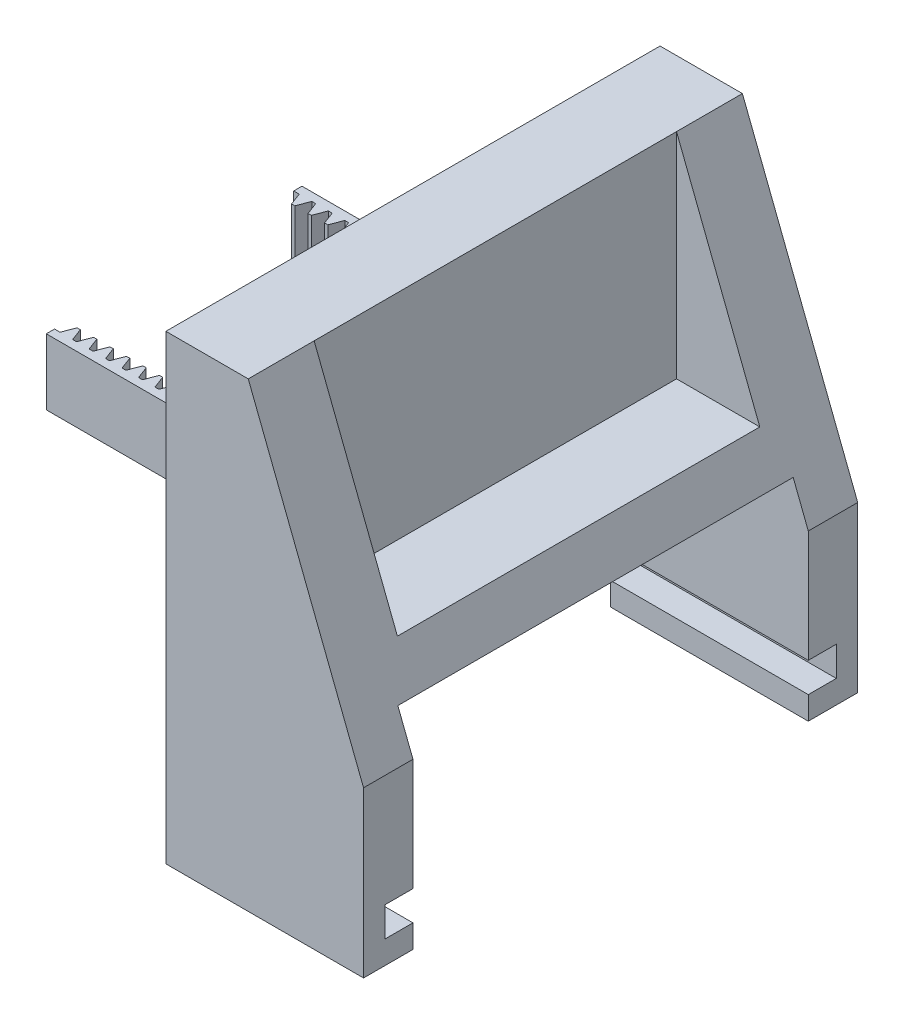
SolidWorks part; units mm, degrees
ref_plane "Front Plane" through (0, 0, 0) normal (0, 0, 1) x (1, 0, 0)
ref_plane "Top Plane" through (0, 0, 0) normal (0, 1, 0) x (1, 0, 0)
ref_plane "Right Plane" through (0, 0, 0) normal (1, 0, 0) x (0, 0, -1)
sketch "Sketch1" plane through (0, 0, 0) normal (0, 0, 1) x (1, 0, 0)
  line L0 (0, 0) -> (0, -28)
  line L1 (0, -28) -> (12, -28)
  line L2 (12, -28) -> (12, -18)
  line L3 (12, -18) -> (5, 0)
  line L4 (5, 0) -> (0, 0)
  dimension "D1" = 28
  dimension "D2" = 12
  dimension "D3" = 10
  dimension "D4" = 5
extrude "Boss-Extrude1" add sketch "Sketch1" against normal blind 30
sketch "Sketch4" plane through (0, 0, 0) normal (-1, 0, 0) x (0, 0, 1)
  line L0 (-30, 0) -> (-30, -28) construction
  line L1 (-27, -15.6386) -> (-3, -15.6386)
  line L2 (-27, -15.6386) -> (-27, -29.6386)
  line L3 (-27, -29.6386) -> (-3, -29.6386)
  line L4 (-3, -15.6386) -> (-3, -29.6386)
  point P4 (-27, -22.6386)
  dimension "D1" = 24
  dimension "D2" = 14
  dimension "D3" = 3
extrude "Cut-Extrude2" cut sketch "Sketch4" against normal blind 25 contours L2 L1 L4 L3
sketch "Sketch5" plane through (0, 0, 0) normal (-1, 0, 0) x (0, 0, 1)
  line L0 (-3, -15.6386) -> (-3, -28) construction
  line L1 (-3, -24.8) -> (-1.3, -24.8)
  line L2 (-3, -24.8) -> (-3, -26.6)
  line L3 (-3, -26.6) -> (-1.3, -26.6)
  line L4 (-1.3, -24.8) -> (-1.3, -26.6)
  line L5 (-3, -28) -> (0, -28) construction
  dimension "D1" = 1.8
  dimension "D2" = 1.7
  dimension "D3" = 1.4
extrude "Cut-Extrude3" cut sketch "Sketch5" against normal blind 15
ref_plane "Plane1" through (0, 0, -15) normal (0, 0, 1) x (1, 0, 0)
mirror "Mirror1" about plane through (0, 0, -15) normal (0, 0, 1) of "Cut-Extrude3"
sketch "Sketch6" plane through (0, 0, -15) normal (0, 0, 1) x (1, 0, 0)
  line L0 (5, 0) -> (5, -13)
  line L1 (5, -13) -> (10.0556, -13)
  line L2 (12, -18) -> (5, 0) construction
  line L3 (10.0556, -13) -> (5, 0)
  dimension "D1" = 13
extrude "Cut-Extrude4" cut sketch "Sketch6" against normal mid plane 22
ref_plane "Plane2" through (0, -15, 0) normal (0, 1, 0) x (1, 0, 0)
sketch "Sketch7" plane through (0, -15, 0) normal (0, 1, 0) x (1, 0, 0)
  line L0 (0, 22.7609) -> (-14.5, 22.7609)
  line L1 (0, 30) -> (0, 0) construction
  line L2 (-14.5, 22.7609) -> (-14.5, 22.2609)
  line L3 (0, 22.7609) -> (0, 22.2609)
  line L4 (0, 22.2609) -> (-0.4, 22.2609)
  line L5 (-0.8812, 21.5119) -> (-1.1644, 22.2609)
  line L6 (-0.4, 22.2609) -> (-0.6812, 21.5119)
  line L7 (-0.6812, 21.5119) -> (-0.8812, 21.5119)
  line L8 (-1.8812, 21.5119) -> (-2.1644, 22.2609)
  line L9 (-1.6812, 21.5119) -> (-1.8812, 21.5119)
  line L10 (-1.4, 22.2609) -> (-1.6812, 21.5119)
  line L11 (-2.8812, 21.5119) -> (-3.1644, 22.2609)
  line L12 (-2.6812, 21.5119) -> (-2.8812, 21.5119)
  line L13 (-2.4, 22.2609) -> (-2.6812, 21.5119)
  line L14 (-3.8812, 21.5119) -> (-4.1644, 22.2609)
  line L15 (-3.6812, 21.5119) -> (-3.8812, 21.5119)
  line L16 (-3.4, 22.2609) -> (-3.6812, 21.5119)
  line L17 (-4.8812, 21.5119) -> (-5.1644, 22.2609)
  line L18 (-4.6812, 21.5119) -> (-4.8812, 21.5119)
  line L19 (-4.4, 22.2609) -> (-4.6812, 21.5119)
  line L20 (-5.8812, 21.5119) -> (-6.1644, 22.2609)
  line L21 (-5.6812, 21.5119) -> (-5.8812, 21.5119)
  line L22 (-5.4, 22.2609) -> (-5.6812, 21.5119)
  line L23 (-6.8812, 21.5119) -> (-7.1644, 22.2609)
  line L24 (-6.6812, 21.5119) -> (-6.8812, 21.5119)
  line L25 (-6.4, 22.2609) -> (-6.6812, 21.5119)
  line L26 (-7.8812, 21.5119) -> (-8.1644, 22.2609)
  line L27 (-7.6812, 21.5119) -> (-7.8812, 21.5119)
  line L28 (-7.4, 22.2609) -> (-7.6812, 21.5119)
  line L29 (-8.8812, 21.5119) -> (-9.1644, 22.2609)
  line L30 (-8.6812, 21.5119) -> (-8.8812, 21.5119)
  line L31 (-8.4, 22.2609) -> (-8.6812, 21.5119)
  line L32 (-9.8812, 21.5119) -> (-10.1644, 22.2609)
  line L33 (-9.6812, 21.5119) -> (-9.8812, 21.5119)
  line L34 (-9.4, 22.2609) -> (-9.6812, 21.5119)
  line L35 (-10.8812, 21.5119) -> (-11.1644, 22.2609)
  line L36 (-10.6812, 21.5119) -> (-10.8812, 21.5119)
  line L37 (-10.4, 22.2609) -> (-10.6812, 21.5119)
  line L38 (-11.8812, 21.5119) -> (-12.1644, 22.2609)
  line L39 (-11.6812, 21.5119) -> (-11.8812, 21.5119)
  line L40 (-11.4, 22.2609) -> (-11.6812, 21.5119)
  line L41 (-12.8812, 21.5119) -> (-13.1644, 22.2609)
  line L42 (-12.6812, 21.5119) -> (-12.8812, 21.5119)
  line L43 (-12.4, 22.2609) -> (-12.6812, 21.5119)
  line L44 (-13.8812, 21.5119) -> (-14.1644, 22.2609)
  line L45 (-13.6812, 21.5119) -> (-13.8812, 21.5119)
  line L46 (-13.4, 22.2609) -> (-13.6812, 21.5119)
  line L47 (-0.8812, 21.5119) -> (-1.8812, 21.5119) construction
  line L48 (-1.1644, 22.2609) -> (-1.4, 22.2609)
  line L49 (-2.1644, 22.2609) -> (-2.4, 22.2609)
  line L50 (-3.1644, 22.2609) -> (-3.4, 22.2609)
  line L51 (-4.1644, 22.2609) -> (-4.4, 22.2609)
  line L52 (-5.1644, 22.2609) -> (-5.4, 22.2609)
  line L53 (-6.1644, 22.2609) -> (-6.4, 22.2609)
  line L54 (-7.1644, 22.2609) -> (-7.4, 22.2609)
  line L55 (-8.1644, 22.2609) -> (-8.4, 22.2609)
  line L56 (-9.1644, 22.2609) -> (-9.4, 22.2609)
  line L57 (-10.1644, 22.2609) -> (-10.4, 22.2609)
  line L58 (-11.1644, 22.2609) -> (-11.4, 22.2609)
  line L59 (-12.1644, 22.2609) -> (-12.4, 22.2609)
  line L60 (-13.1644, 22.2609) -> (-13.4, 22.2609)
  line L61 (-14.1644, 22.2609) -> (-14.5, 22.2609)
  dimension "D1" = 0.8
  dimension "D4" = 0.2
  dimension "D2" = 14.5
  dimension "D3" = 0.5
  dimension "D5" = 1
  dimension "D6" = 0.4
extrude "Boss-Extrude2" add sketch "Sketch7" along normal blind 4
mirror "Mirror2" about plane through (0, 0, -15) normal (0, 0, 1) of "Boss-Extrude2"
